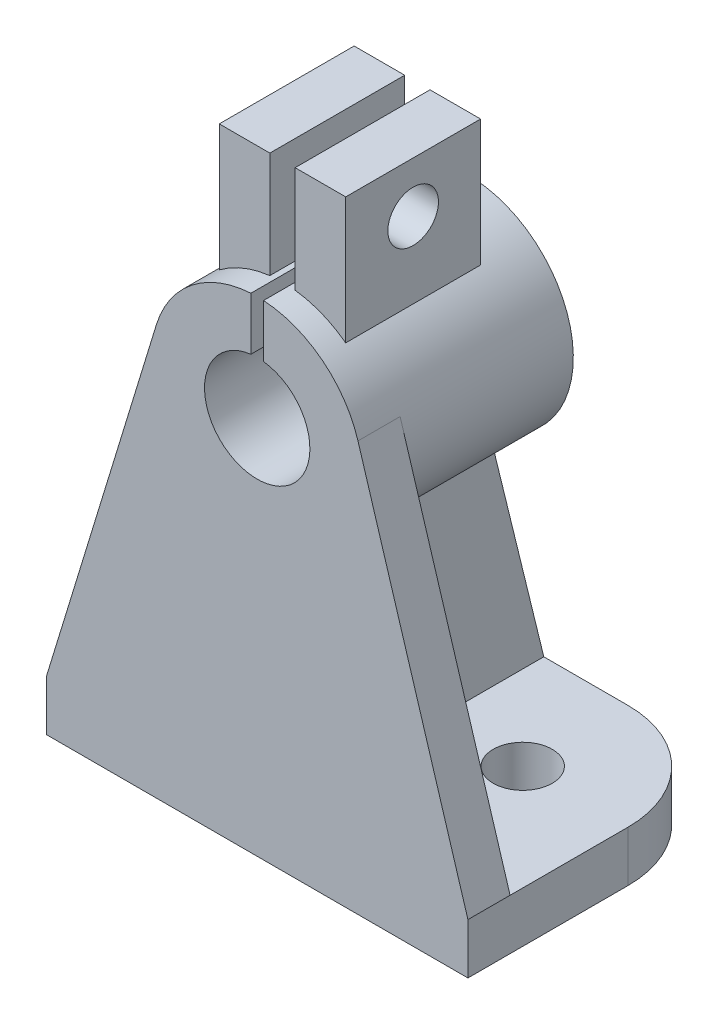
SolidWorks part; units mm, degrees
ref_plane "Front Plane" through (0, 0, 0) normal (0, 0, 1) x (1, 0, 0)
ref_plane "Top Plane" through (0, 0, 0) normal (0, 1, 0) x (1, 0, 0)
ref_plane "Right Plane" through (0, 0, 0) normal (1, 0, 0) x (0, 0, -1)
sketch "Sketch1" plane through (0, 0, 0) normal (0, 1, 0) x (1, 0, 0)
  line L1 (-50, 63) -> (50, 63)
  line L2 (-50, 63) -> (-50, 0)
  line L3 (-50, 0) -> (50, 0)
  line L4 (50, 63) -> (50, 0)
  dimension "D1" = 100
  dimension "D2" = 63
  dimension "D3" = 50
extrude "Boss-Extrude1" add sketch "Sketch1" along normal blind 12
sketch "Sketch2" plane through (0, 0, 0) normal (0, 0, 1) x (1, 0, 0)
  line L0 (-50, 0) -> (50, 0) construction
  circle A0 centre (0, 90) radius 25
  point P4 (0, 0)
  dimension "D1" = 50
  dimension "D2" = 90
extrude "Boss-Extrude2" add sketch "Sketch2" against normal blind 50 separate body
sketch "Sketch3" plane through (0, 0, 0) normal (0, 0, 1) x (1, 0, 0)
  line L0 (-50, 12) -> (50, 12) construction
  line L1 (-50, 12) -> (50, 12)
  line L2 (-50, 12) -> (-23.9068, 97.312)
  line L3 (50, 12) -> (23.9068, 97.312)
  circle A0 centre (0, 90) radius 25 construction
  arc A1 (23.9068, 97.312) -> (-23.9068, 97.312) centre (0, 90) ccw
extrude "Boss-Extrude3" add sketch "Sketch3" against normal blind 10
sketch "Sketch4" plane through (0, 0, 0) normal (1, 0, 0) x (0, 0, -1)
  line L0 (63, 12) -> (50, 65)
rib "Rib1" sketch "Sketch4" sketch "Sketch4" thickness 10 extrusion direction parallel to sketch draft on no parameters "D1"=10
sketch "Sketch5" plane through (0, 0, 0) normal (1, 0, 0) x (0, 0, -1)
  line L0 (50, 65) -> (50, 115) construction
  line L1 (6, 140) -> (38, 140)
  line L2 (6, 140) -> (6, 108)
  line L3 (6, 108) -> (38, 108)
  line L4 (38, 140) -> (38, 108)
  line L8 (0, 12) -> (0, 97.312) construction
  point P8 (50, 90)
  dimension "D1" = 32
  dimension "D2" = 6
  dimension "D3" = 32
  dimension "D4" = 50
extrude "Boss-Extrude4" add sketch "Sketch5" along normal blind 12 from offset 3 separate body
extrude "Boss-Extrude5" add sketch "Sketch5<2>" along normal blind 12 from offset 3
sketch "Sketch5<2>" plane through (0, 0, 0) normal (1, 0, 0) x (0, 0, -1) same geometry as "Sketch5"
mirror "Mirror7" about plane through (0, 0, 0) normal (1, 0, 0) of "Boss-Extrude5"
sketch "Sketch6" plane through (0, 0, -50) normal (0, 0, -1) x (-1, 0, 0)
  line L0 (0, 0) -> (0, 170.9548) construction
  line L1 (-1.5, 140) -> (1.5, 140)
  line L2 (-1.5, 140) -> (-1.5, 93.9021)
  line L3 (-1.5, 93.9021) -> (1.5, 93.9021)
  line L4 (1.5, 140) -> (1.5, 93.9021)
  line L5 (15, 140) -> (3, 140) construction
  dimension "D1" = 3
extrude "Cut-Extrude1" cut sketch "Sketch6" against normal through all
hole_wizard "Hole1" positions "Sketch9" profile "Sketch8" legacy end condition through all
sketch "Sketch9" plane through (0, 0, -50) normal (0, 0, -1) x (-1, 0, 0)
  point P0 (0, 90)
sketch "Sketch8" plane through (0, 90, -50) normal (1, 0, 0) x (0, 1, 0)
  line L0 (0, 0) -> (0, 50)
  line L1 (0, 50) -> (12.5, 50)
  line L2 (12.5, 50) -> (12.5, 0)
  line L3 (12.5, 0) -> (0, 0)
  line L4 (0, 110) -> (0, -10) construction
  dimension "Diameter" = 25
  dimension "Depth" = 50
hole_wizard "Hole2" positions "Sketch12" profile "Sketch11" legacy end condition through all
sketch "Sketch12" plane through (-15, 0, 0) normal (-1, 0, 0) x (0, 0, 1)
  line L0 (-38, 140) -> (-6, 140) construction
  line L2 (-38, 110) -> (-38, 140) construction
  point P0 (-22, 128)
  dimension "D1" = 12
  dimension "D2" = 16
sketch "Sketch11" plane through (-15, 128, -22) normal (0, 1, 0) x (0, 0, 1)
  line L0 (0, 0) -> (0, 65)
  line L1 (0, 65) -> (6, 65)
  line L2 (6, 65) -> (6, 0)
  line L3 (6, 0) -> (0, 0)
  line L4 (0, 110) -> (0, -10) construction
  dimension "Diameter" = 12
  dimension "Depth" = 65
hole_wizard "Hole3" positions "Sketch15" profile "Sketch14" legacy end condition through all
sketch "Sketch15" plane through (0, 12, 0) normal (0, 1, 0) x (1, 0, 0)
  line L1 (-23.9068, 0) -> (-50, 0) construction
  point P0 (-25, 38)
  point P2 (25, 38)
  point P5 (0, 0)
  dimension "D1" = 50
  dimension "D2" = 38
  dimension "D3" = 25
sketch "Sketch14" plane through (-25, 12, -38) normal (1, 0, 0) x (0, 0, 1)
  line L0 (0, 0) -> (0, 12)
  line L1 (0, 12) -> (7, 12)
  line L2 (7, 12) -> (7, 0)
  line L3 (7, 0) -> (0, 0)
  line L4 (0, 110) -> (0, -10) construction
  dimension "Diameter" = 14
  dimension "Depth" = 12
fillet "Fillet1" radius 25 2 edges at (-50, 6, -63) (50, 6, -63)
